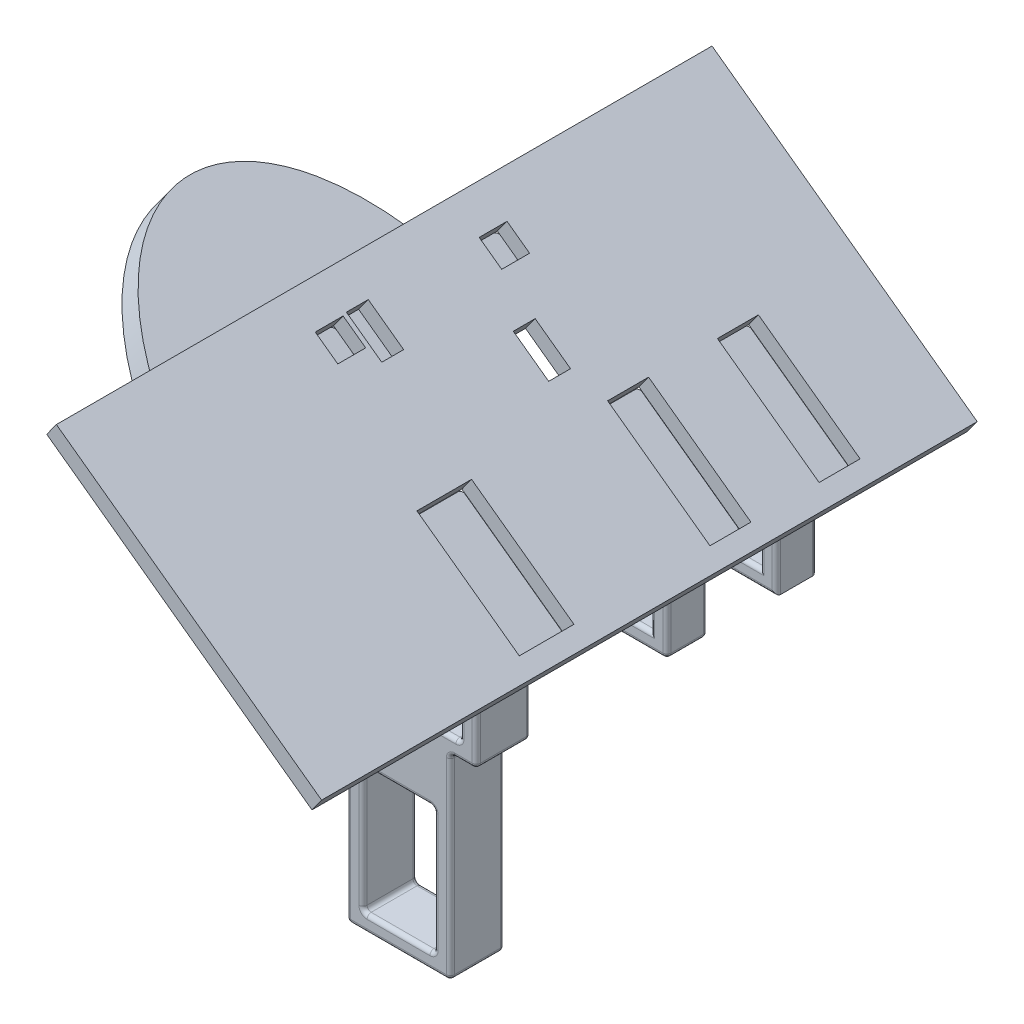
SolidWorks part; units mm, degrees
ref_plane "Front Plane" through (0, 0, 0) normal (0, 0, 1) x (1, 0, 0)
ref_plane "Top Plane" through (0, 0, 0) normal (0, 1, 0) x (1, 0, 0)
ref_plane "Right Plane" through (0, 0, 0) normal (1, 0, 0) x (0, 0, -1)
sketch "Sketch3" plane through (0, 0, 0) normal (0, 0, 1) x (1, 0, 0)
  line L0 (-14.25, 5.65) -> (14.25, 5.65) construction
  line L1 (-11.25, -2.65) -> (11.25, -2.65)
  line L2 (-11.25, -2.65) -> (-11.25, 2.65)
  line L3 (-11.25, 2.65) -> (11.25, 2.65)
  line L4 (11.25, -2.65) -> (11.25, 2.65)
  line L5 (-11.25, -2.65) -> (11.25, 2.65) construction
  line L6 (-11.25, 2.65) -> (11.25, -2.65) construction
  line L7 (-6.5, -15.45) -> (6.5, -15.45)
  line L8 (-6.5, -15.45) -> (-6.5, -38.55)
  line L9 (-6.5, -38.55) -> (6.5, -38.55)
  line L10 (6.5, -15.45) -> (6.5, -38.55)
  line L11 (-6.5, -15.45) -> (6.5, -38.55) construction
  line L12 (-6.5, -38.55) -> (6.5, -15.45) construction
  line L13 (14.25, -5.65) -> (14.25, 5.65)
  line L15 (-14.25, -5.65) -> (-14.25, 5.65)
  line L16 (9.5, -12.45) -> (9.5, -41.55)
  line L17 (-9.5, -41.55) -> (9.5, -41.55)
  line L18 (-9.5, -12.45) -> (-9.5, -41.55)
  line L20 (-9.5, -12.45) -> (9.5, -12.45) construction
  line L21 (-14.25, -5.65) -> (14.25, -5.65) construction
  line L22 (-9.5, -12.45) -> (-9.5, -5.65)
  line L23 (-9.5, -5.65) -> (-14.25, -5.65)
  line L24 (14.25, -5.65) -> (9.5, -5.65)
  line L25 (9.5, -5.65) -> (9.5, -12.45)
  line L26 (-14.25, 5.65) -> (1.7036, 27.6082)
  line L27 (1.7036, 27.6082) -> (20.3571, 14.0557)
  line L28 (20.3571, 14.0557) -> (14.25, 5.65)
  line L29 (0, -41.55) -> (0, 5.7) construction
  point P0 (0, 0)
  point P5 (0, -27)
  dimension "D1" = 22.5
  dimension "D2" = 5.3
  dimension "D3" = 27
  dimension "D4" = 13
  dimension "D5" = 23.1
  dimension "D7" = 3
  dimension "D8" = 54
  dimension "D9" = 10.39
  dimension "D10" = 8.4057
  dimension "D11" = 19
  dimension "D6" = 3
extrude "Boss-Extrude1" add sketch "Sketch3" along normal blind 9.9
sketch "Sketch4" plane through (13.7171, 18.8799, 0) normal (0.5878, 0.809, 0) x (0.809, -0.5878, 0)
  line L0 (-3.321, 0) -> (-3.321, -9.9) construction
  line L1 (8.2075, 0) -> (-14.8495, 0) construction
  line L2 (8.2075, -9.9) -> (-14.8495, -9.9) construction
  line L3 (-14.8495, -4.95) -> (8.2075, -4.95) construction
  line L4 (-14.8495, -9.9) -> (-14.8495, 0) construction
  line L5 (8.2075, -9.9) -> (8.2075, 0) construction
  line L7 (-48.321, 71.1) -> (11.679, 71.1)
  line L8 (-48.321, 71.1) -> (-48.321, -48.9)
  line L9 (-48.321, -48.9) -> (11.679, -48.9)
  line L10 (11.679, 71.1) -> (11.679, -48.9)
  line L11 (-48.321, 71.1) -> (11.679, -48.9) construction
  line L12 (-48.321, -48.9) -> (11.679, 71.1) construction
  point P12 (-3.321, -4.95)
  point P13 (-18.321, 11.1)
  dimension "D1" = 120
  dimension "D2" = 60
  dimension "D3" = 16.05
  dimension "D4" = 15
extrude "Boss-Extrude2" add sketch "Sketch4" along normal blind 3
sketch "Sketch7" plane through (13.7171, 18.8799, 0) normal (-0.5878, -0.809, 0) x (0.809, -0.5878, 0)
  line L0 (-14.9179, -10.8) -> (-63.9179, -10.8) construction
  line L6 (-36.7569, 1.65) -> (-41.8569, 1.65)
  line L7 (-36.7569, 1.65) -> (-36.7569, 6.75)
  line L8 (-36.7569, 6.75) -> (-41.8569, 6.75)
  line L9 (-41.8569, 1.65) -> (-41.8569, 6.75)
  line L10 (-36.7569, 1.65) -> (-41.8569, 6.75) construction
  line L11 (-36.7569, 6.75) -> (-41.8569, 1.65) construction
  line L12 (-48.321, -71.1) -> (-48.321, 48.9) construction
  line L13 (-36.7569, -23.25) -> (-36.7569, -28.35)
  line L14 (-36.7569, -23.25) -> (-41.8569, -23.25)
  line L15 (-41.8569, -23.25) -> (-41.8569, -28.35)
  line L16 (-36.7569, -28.35) -> (-41.8569, -28.35)
  point P4 (-39.3069, 4.2)
  dimension "D1" = 15
  dimension "D2" = 9.0141
  dimension "D3" = 5.1
  dimension "D4" = 5.1
  dimension "D5" = 5.1
  dimension "D6" = 6.4641
  dimension "D7" = 12.45
extrude "Boss-Extrude3" add sketch "Sketch7" along normal blind 24.5 and the other way blind 3
sketch "Sketch8" plane through (-0.6837, -0.941, 0) normal (-0.5878, -0.809, 0) x (0.809, -0.5878, 0)
  line L2 (-23.3069, 5.8504) -> (-23.3069, -28.0504)
  line L3 (-23.3069, 5.8504) -> (-34.6206, 17.1641)
  line L4 (-23.3069, -28.0504) -> (-34.6206, -39.3641)
  line L6 (11.679, -71.1) -> (-48.321, -71.1) construction
  line L7 (-48.321, 48.9) -> (11.679, -71.1) construction
  line L8 (-18.321, -11.1) -> (-48.321, -11.1) construction
  line L9 (11.679, 48.9) -> (11.679, -71.1) construction
  ellipse E0 centre (-23.3069, -11.1) end of major axis (-72.2778, -11.1) minor radius 29.05 (-34.6206, 17.1641) -> (-34.6206, -39.3641) ccw
  dimension "D1" = 4.9859
  dimension "D2" = 28.2641
  dimension "D3" = 23.9569
  dimension "D4" = 45
  dimension "D5" = 16
  dimension "D6" = 48.9709
  dimension "D7" = 60
  dimension "D8" = 34.9859
extrude "Boss-Extrude4" add sketch "Sketch8" along normal blind 5
ref_plane "Plane1" through (0, 0, -25) normal (0, 0, -1) x (-1, 0, 0)
ref_plane "Plane2" through (0, 0, -45) normal (0, 0, -1) x (-1, 0, 0)
sketch "Sketch9" plane through (0, 0, -25) normal (0, 0, -1) x (-1, 0, 0)
  line L0 (-22.1204, 16.4827) -> (-14.25, 5.65)
  line L2 (-3.467, 30.0353) -> (14.25, 5.65)
  line L3 (14.25, 5.65) -> (14.25, -5.65)
  line L4 (14.25, -5.65) -> (9.5, -5.65)
  line L5 (9.5, -5.65) -> (-14.25, -5.65)
  line L6 (-14.25, -5.65) -> (-14.25, 5.65)
  line L7 (-11.25, 2.65) -> (11.25, 2.65)
  line L8 (11.25, 2.65) -> (11.25, -2.65)
  line L9 (11.25, -2.65) -> (-11.25, -2.65)
  line L10 (-11.25, -2.65) -> (-11.25, 2.65)
  line L12 (-24.929, 14.4422) -> (-23.1656, 12.0152) construction
  line L13 (-24.929, 14.4422) -> (23.6121, 49.7094) construction
  line L14 (-22.1204, 16.4827) -> (-3.467, 30.0353)
  dimension "D1" = 3.4715
extrude "Boss-Extrude5" add sketch "Sketch9" along normal blind 7.4 contours L10 L9 L8 L7 | L0 L6 L5 L4 L3 L2 L14 region at (0, 0, -25)
sketch "Sketch10" plane through (0, 0, -45) normal (0, 0, -1) x (-1, 0, 0)
  line L0 (-22.1204, 16.4827) -> (-14.25, 5.65)
  line L1 (-22.1204, 16.4827) -> (-3.467, 30.0353)
  line L2 (-3.467, 30.0353) -> (14.25, 5.65)
  line L3 (14.25, 5.65) -> (14.25, -5.65)
  line L6 (-14.25, -5.65) -> (-14.25, 5.65)
  line L7 (-11.25, 2.65) -> (11.25, 2.65)
  line L8 (11.25, 2.65) -> (11.25, -2.65)
  line L9 (11.25, -2.65) -> (-11.25, -2.65)
  line L10 (-11.25, -2.65) -> (-11.25, 2.65)
  line L11 (-24.929, 14.4422) -> (23.6121, 49.7094) construction
  line L13 (-20.3571, 14.0557) -> (-14.25, 5.65) construction
  line L14 (-14.25, -5.65) -> (-14.25, 5.65) construction
  line L16 (-1.7036, 27.6082) -> (14.25, 5.65) construction
  line L17 (14.25, 5.65) -> (14.25, -5.65) construction
  line L18 (-14.25, -5.65) -> (14.25, -5.65)
extrude "Boss-Extrude6" add sketch "Sketch10" along normal blind 7.4
sketch "Sketch11" plane through (13.7171, 18.8799, 0) normal (-0.5878, -0.809, 0) x (0.809, -0.5878, 0)
  line L0 (-14.8495, 9.9) -> (-14.8495, 0) construction
  line L9 (8.2075, 9.9) -> (8.2075, 0) construction
  line L10 (-48.321, 48.9) -> (11.679, 48.9) construction
  line L11 (-14.8495, -32.4) -> (-14.8495, -25) construction
  line L12 (11.679, 48.9) -> (11.679, -71.1) construction
  line L13 (8.2075, 9.9) -> (-14.8495, 9.9) construction
  line L24 (-14.901, 9.95) -> (8.259, 9.95)
  line L25 (-14.901, 9.95) -> (-14.901, -0.05)
  line L26 (-14.901, -0.05) -> (8.259, -0.05)
  line L27 (8.259, 9.95) -> (8.259, -0.05)
  line L29 (8.2075, 0) -> (-14.8495, 0) construction
  line L30 (-14.8995, -24.95) -> (8.2575, -24.95)
  line L35 (-14.8995, -24.95) -> (-14.8995, -32.45)
  line L36 (-14.8995, -32.45) -> (8.2575, -32.45)
  line L37 (8.2575, -24.95) -> (8.2575, -32.45)
  line L38 (-14.8495, -32.4) -> (8.2075, -32.4) construction
  line L39 (8.2075, -32.4) -> (8.2075, -25) construction
  line L40 (-14.8495, -25) -> (8.2075, -25) construction
  line L42 (-14.771, -44.95) -> (8.229, -44.95)
  line L43 (-14.771, -44.95) -> (-14.771, -52.45)
  line L44 (-14.771, -52.45) -> (8.229, -52.45)
  line L45 (8.229, -44.95) -> (8.229, -52.45)
  line L46 (11.679, -71.1) -> (-48.321, -71.1) construction
  line L47 (-14.8495, -45) -> (-14.8495, -52.4) construction
  line L48 (-14.8495, -52.4) -> (8.2075, -52.4) construction
  dimension "D2" = 38.95
  dimension "D3" = 3.42
  dimension "D4" = 23.16
  dimension "D5" = 23.157
  dimension "D6" = 7.5
  dimension "D7" = 3.45
  dimension "D8" = 23
  dimension "D9" = 3.4215
  dimension "D10" = 7.5
  dimension "D11" = 73.85
  dimension "D12" = 18.65
  dimension "D13" = 10
  dimension "D14" = 0.0515
  dimension "D15" = 0.0515
  dimension "D16" = 0.05
  dimension "D17" = 0.05
  dimension "D18" = 0.05
  dimension "D19" = 0.05
  dimension "D20" = 0.05
  dimension "D21" = 0.05
  dimension "D22" = 0.0785
  dimension "D23" = 0.05
extrude "Cut-Extrude4" cut sketch "Sketch7<2>" against normal blind 10
sketch "Sketch7<2>" plane through (13.7171, 18.8799, 0) normal (-0.5878, -0.809, 0) x (0.809, -0.5878, 0) same geometry as "Sketch7"
sketch "Sketch6" plane through (13.7171, 18.8799, 0) normal (-0.5878, -0.809, 0) x (0.809, -0.5878, 0)
  line L1 (-20.971, -23.075) -> (-28.971, -23.075)
  line L2 (-20.971, -23.075) -> (-20.971, -19.075)
  line L3 (-20.971, -19.075) -> (-28.971, -19.075)
  line L4 (-28.971, -23.075) -> (-28.971, -19.075)
  line L5 (-34.071, -3.125) -> (-42.071, -3.125)
  line L6 (-34.071, -3.125) -> (-34.071, 0.875)
  line L7 (-34.071, 0.875) -> (-42.071, 0.875)
  line L10 (-48.321, -71.1) -> (-48.321, 48.9) construction
  line L11 (-42.071, 0.875) -> (-42.071, -3.125)
  line L12 (-48.321, 48.9) -> (11.679, 48.9) construction
  dimension "D1" = 8
  dimension "D2" = 6.25
  dimension "D3" = 4
  dimension "D4" = 48.025
  dimension "D5" = 15.95
  dimension "D6" = 19.35
  dimension "D7" = 8
  dimension "D8" = 4
extrude "Cut-Extrude1" cut sketch "Sketch6" against normal up to surface (3 mm away) up to face at (-16.3195, 44.411, 4.2)
fillet "Fillet1" radius 0.75 50 edges at (-11.25, 0, 9.9) (-11.25, 0, 0) (-11.875, -5.65, 9.9) (-11.875, -5.65, 0) (11.875, -5.65, 9.9) (11.875, -5.65, 0) (0, -38.55, 9.9) (0, -38.55, 0) (-6.5, -38.55, 4.95) (-6.5, -27, 9.9) (-6.5, -27, 0) (6.5, -27, 9.9) (6.5, -38.55, 4.95) (6.5, -27, 0) (-6.5, -15.45, 4.95) (0, -15.45, 9.9) (6.5, -15.45, 4.95) (0, -15.45, 0) (0, -41.55, 9.9) (0, -41.55, 0) (9.5, -41.55, 4.95) (9.5, -23.6, 9.9) (9.5, -5.65, 4.95) (9.5, -23.6, 0) (14.25, -5.65, 4.95) (14.25, 0, 9.9) (14.25, 5.65, 4.95) (14.25, 0, 0) (-9.5, -5.65, 4.95) (-9.5, -23.6, 9.9) (-9.5, -41.55, 4.95) (-9.5, -23.6, 0) (-14.25, 5.65, 4.95) (-14.25, 0, 9.9) (-14.25, -5.65, 4.95) (-14.25, 0, 0) (11.25, 0, 9.9) (11.25, 0, 0) (-11.25, 2.65, 4.95) (0, 2.65, 9.9) (11.25, 2.65, 4.95) (0, 2.65, 0) (11.25, -2.65, 4.95) (0, -2.65, 9.9) (-11.25, -2.65, 4.95) (0, -2.65, 0) (17.3035, 9.8528, 9.9) (17.3035, 9.8528, 0) (-6.2732, 16.6291, 9.9) (-6.2732, 16.6291, 0)
fillet "Fillet4" radius 0.75 48 edges at (14.25, 5.65, -48.7) (-14.25, 5.65, -48.7) (17.3035, 9.8528, -45) (14.25, 0, -45) (-14.25, 0, -45) (-6.2732, 16.6291, -45) (-11.25, 0, -45) (0, -2.65, -45) (11.25, 0, -45) (0, 2.65, -45) (-14.25, 0, -52.4) (14.25, 0, -52.4) (17.3035, 9.8528, -52.4) (-6.2732, 16.6291, -52.4) (0, -2.65, -52.4) (-11.25, 0, -52.4) (0, 2.65, -52.4) (11.25, 0, -52.4) (-11.25, -2.65, -48.7) (11.25, 2.65, -48.7) (-11.25, 2.65, -48.7) (-14.25, -5.65, -48.7) (0, -5.65, -45) (0, -5.65, -52.4) (17.3035, 9.8528, -25) (-14.25, -5.65, -28.7) (-14.25, 0, -32.4) (-14.25, 5.65, -28.7) (-14.25, 0, -25) (-6.2732, 16.6291, -25) (11.25, 2.65, -28.7) (11.25, 0, -25) (0, 2.65, -25) (-11.25, -2.65, -28.7) (0, -5.65, -25) (-11.25, 0, -25) (0, -2.65, -25) (-11.25, 0, -32.4) (14.25, -5.65, -28.7) (14.25, 5.65, -28.7) (14.25, 0, -25) (14.25, 0, -32.4) (17.3035, 9.8528, -32.4) (-6.2732, 16.6291, -32.4) (0, -5.65, -32.4) (0, -2.65, -32.4) (11.25, 0, -32.4) (0, 2.65, -32.4)
chamfer "Chamfer1" distance 2 angle 45 8 edges at (-32.4836, 22.163, 1.65) (-30.4206, 20.6642, 4.2) (-32.4836, 22.163, 6.75) (-34.5466, 23.6619, 4.2) (-32.4836, 22.163, -23.25) (-30.4206, 20.6642, -25.8) (-32.4836, 22.163, -28.35) (-34.5466, 23.6619, -25.8)
fillet "Fillet6" radius 0.75 8 edges at (-22.6325, 31.3837, 1.65) (-22.6325, 31.3837, 6.75) (-26.7584, 34.3814, 1.65) (-26.7584, 34.3814, 6.75) (-22.6325, 31.3837, -23.25) (-26.7584, 34.3814, -23.25) (-22.6325, 31.3837, -28.35) (-26.7584, 34.3814, -28.35)
extrude "Cut-Extrude5" cut sketch "Sketch11" against normal blind 10
